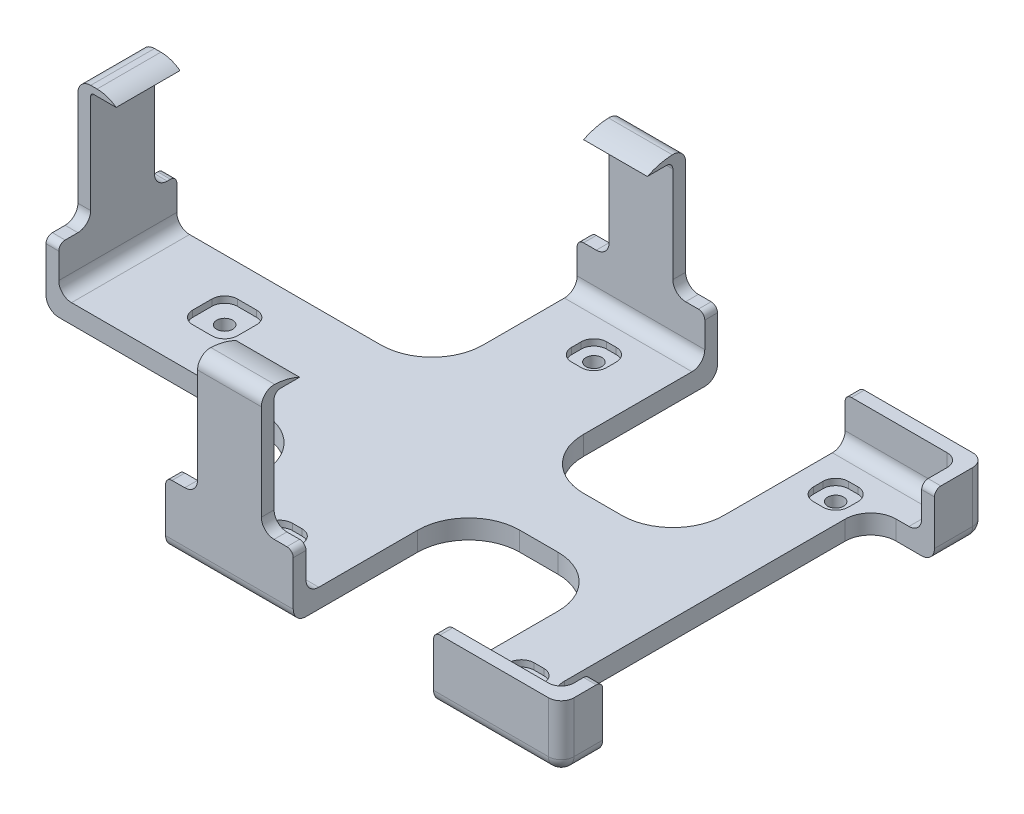
SolidWorks part; units mm, degrees
note: The reader was unsure of these and kept them because the rebuilt part matched: shared geometry of "Sketch1<3>".
ref_plane "Front Plane" through (0, 0, 0) normal (0, 0, 1) x (1, 0, 0)
ref_plane "Top Plane" through (0, 0, 0) normal (0, 1, 0) x (1, 0, 0)
ref_plane "Right Plane" through (0, 0, 0) normal (1, 0, 0) x (0, 0, -1)
sketch "Sketch1" plane through (0, 0, 0) normal (0, 1, 0) x (1, 0, 0)
  line L0 (100, 0) -> (0, 0)
  line L1 (0, 0) -> (0, -62.5)
  line L2 (0, -62.5) -> (100, -62.5)
  line L3 (100, -62.5) -> (100, 0)
  line L4 (102, 2) -> (-2, 2)
  line L5 (-2, 2) -> (-2, -64.5)
  line L6 (-2, -64.5) -> (102, -64.5)
  line L7 (102, -64.5) -> (102, 2)
  dimension "D1" = 62.5
  dimension "D2" = 100
  dimension "D3" = 2
extrude "Boss-Extrude1" add sketch "Sketch1" along normal blind 3 contours L0 L1 L2 L3
extrude "Boss-Extrude2" add sketch "Sketch1<3>" along normal blind 10
sketch "Sketch1<3>" plane through (0, 0, 0) normal (0, 1, 0) x (1, 0, 0) same geometry as "Sketch1"
sketch "Sketch2" plane through (102, 0, 0) normal (1, 0, 0) x (0, 0, -1)
  line L0 (-66, 5) -> (-58, 5) construction
  line L1 (-32, 0) -> (-32, 7.4819) construction
  line L2 (2, 5) -> (-6, 5) construction
  line L3 (-58, 0) -> (-58, 10)
  line L4 (-6, 0) -> (-6, 10)
  line L5 (-64.5, 10) -> (2, 10) construction
  line L6 (-58, 10) -> (-6, 10)
  line L7 (-64.5, 0) -> (2, 0) construction
  line L8 (-58, 0) -> (-6, 0)
  dimension "D1" = 8
extrude "Cut-Extrude1" cut sketch "Sketch2" against normal blind 10
sketch "Sketch5" plane through (0, 0, 64.5) normal (0, 0, 1) x (1, 0, 0)
  line L0 (50, 10) -> (50, 28) construction
  line L1 (-2, 10) -> (102, 10) construction
  line L2 (50, 10) -> (45, 10)
  line L3 (50, 10) -> (55, 10)
  line L4 (45, 10) -> (45, 28)
  line L5 (45, 28) -> (55, 28)
  line L6 (55, 28) -> (55, 10)
  dimension "D1" = 18
  dimension "D2" = 5
  dimension "D3" = 5
extrude "Boss-Extrude3" add sketch "Sketch5" against normal blind 2
sketch "Sketch7" plane through (55, 0, 0) normal (1, 0, 0) x (0, 0, -1)
  line L0 (-62.5, 28) -> (-58.5, 28)
  line L1 (-58.5, 28) -> (-58.5, 29)
  line L2 (-64.5, 28) -> (-64.5, 29)
  line L3 (-64.5, 29) -> (-58.5, 29)
  line L4 (-62.5, 28) -> (-64.5, 28) construction
  line L5 (-62.5, 28) -> (-64.5, 28)
  dimension "D1" = 1
  dimension "D2" = 4
extrude "Boss-Extrude4" add sketch "Sketch7" against normal up to surface (10 mm away) up to face at (45, 19, 63.5)
fillet "Fillet2" radius 10 1 edges at (50, 29, 58.5)
fillet "Fillet4" radius 1 1 edges at (50, 28, 62.5)
fillet "Fillet5" [suppressed] radius 1
sketch "Sketch9" plane through (0, 3, 0) normal (0, 1, 0) x (1, 0, 0)
  line L0 (-2, -32) -> (92, -32) construction
  line L1 (-2, 2) -> (-2, -64.5) construction
  line L2 (92, -58) -> (92, -6) construction
ref_plane "Plane1" through (0, 0, 32) normal (0, 0, 1) x (1, 0, 0)
mirror "Mirror5" about plane through (0, 0, 32) normal (0, 0, 1) of "Boss-Extrude4", "Boss-Extrude3"
fillet "Fillet9" radius 10 1 edges at (50, 29, 5.5)
fillet "Fillet10" radius 0.5 1 edges at (50, 28, 1.5)
fillet "Fillet11" radius 1 1 edges at (50, 29, -0.5)
sketch "Sketch10" plane through (-2, 0, 0) normal (-1, 0, 0) x (0, 0, 1)
  line L0 (31.25, 10) -> (31.25, 28) construction
  line L1 (-2, 10) -> (64.5, 10) construction
  line L2 (36.25, 10) -> (26.25, 10)
  line L3 (26.25, 10) -> (26.25, 28)
  line L4 (26.25, 28) -> (36.25, 28)
  line L5 (36.25, 10) -> (36.25, 28)
  dimension "D1" = 18
  dimension "D2" = 5
extrude "Boss-Extrude5" add sketch "Sketch10" against normal up to surface (2 mm away) up to face at (0, 6.5, 31.25)
sketch "Sketch11" plane through (0, 0, 26.25) normal (0, 0, -1) x (-1, 0, 0)
  line L0 (2, 28) -> (2, 29)
  line L1 (0, 28) -> (-4, 28)
  line L2 (0, 28) -> (2, 28) construction
  line L3 (0, 28) -> (2, 28)
  line L4 (-4, 28) -> (-4, 29)
  line L5 (-4, 29) -> (2, 29)
  dimension "D1" = 1
  dimension "D2" = 4
extrude "Boss-Extrude6" add sketch "Sketch11" against normal up to surface (10 mm away) up to face at (-1, 19, 36.25)
fillet "Fillet12" radius 5 1 edges at (4, 29, 31.25)
fillet "Fillet13" radius 0.5 1 edges at (0, 28, 31.25)
fillet "Fillet14" radius 2 1 edges at (-2, 29, 31.25)
sketch "Sketch14" plane through (0, 3, 0) normal (0, 1, 0) x (1, 0, 0)
  line L0 (0, -62.5) -> (100, -62.5) construction
  line L1 (0, -62.5) -> (100, -62.5) construction
  line L2 (50, -62.5) -> (50, -51.3755) construction
  line L3 (50, -62.5) -> (40, -62.5) construction
  line L4 (0, 0) -> (0, -62.5) construction
  line L5 (0, 0) -> (0, -62.5) construction
  line L6 (0, -31.25) -> (0, -41.25) construction
  line L7 (40, -62.5) -> (40, -41.25)
  line L8 (40, -41.25) -> (0, -41.25)
  line L9 (0, -41.25) -> (-2, -41.25)
  line L10 (-2, -36.25) -> (-2, -64.5) construction
  line L11 (-2, -41.25) -> (-2, -64.5)
  line L12 (-2, -64.5) -> (40, -64.5)
  line L13 (-2, -64.5) -> (45, -64.5) construction
  line L14 (40, -64.5) -> (40, -62.5)
  dimension "D1" = 10
  dimension "D2" = 10
extrude "Cut-Extrude2" cut sketch "Sketch14" against normal through all both and the other way through all
fillet "Fillet15" radius 8 1 edges at (40, 1.5, 41.25)
mirror "Mirror6" about plane through (0, 0, 32) normal (0, 0, 1) of "Cut-Extrude2"
fillet "Fillet16" radius 8 1 edges at (40, 1.5, 22.75)
sketch "Sketch17" plane through (0, 3, 0) normal (0, 1, 0) x (1, 0, 0)
  line L0 (55, -5.5) -> (55, -1.1411) construction
  line L1 (55, -5.5) -> (55, -1.1411) construction
  line L3 (100, 0) -> (40, 0) construction
  line L4 (100, 0) -> (40, 0) construction
  line L5 (55, 0) -> (60, 0) construction
  line L6 (60, 0) -> (60, -27)
  line L7 (-2, -32) -> (92, -32) construction
  line L8 (60, -27) -> (82, -27)
  line L9 (92, -58) -> (92, -6) construction
  line L10 (82, -27) -> (82, 2)
  line L11 (102, 2) -> (-2, 2) construction
  line L12 (82, 2) -> (60, 2)
  line L13 (60, 2) -> (60, 0)
  dimension "D1" = 5
  dimension "D2" = 5
  dimension "D3" = 10
extrude "Cut-Extrude5" cut sketch "Sketch17" against normal through all both and the other way through all
mirror "Mirror7" about plane through (0, 0, 32) normal (0, 0, 1) of "Cut-Extrude5"
fillet "Fillet17" radius 8 4 edges at (82, 1.5, 37) (82, 1.5, 27) (60, 1.5, 27) (60, 1.5, 37)
fillet "Fillet18" radius 4 2 edges at (92, 1.5, 58) (92, 1.5, 6)
fillet "Fillet19" [suppressed] radius 2
fillet "Fillet20" [suppressed] radius 2
fillet "Fillet21" [suppressed] radius 4
fillet "Fillet22" radius 2 2 edges at (100, 6.5, 62.5) (100, 6.5, 0)
fillet "Fillet23" [suppressed] radius 2
fillet "Fillet24" radius 2 2 edges at (102, 5, 64.5) (102, 5, -2)
sketch "Sketch19" plane through (0, 3, 0) normal (0, 1, 0) x (1, 0, 0)
  line L0 (16, -41.25) -> (16, -48.9913) construction
  line L1 (32, -41.25) -> (0, -41.25) construction
  line L2 (12, -41.25) -> (12, -45.25)
  line L3 (12, -45.25) -> (16, -45.25)
  line L4 (16, -45.25) -> (16, -41.25)
  line L5 (12, -41.25) -> (16, -41.25)
  dimension "D1" = 4
  dimension "D2" = 4
sketch "Sketch21" plane through (0, 3, 0) normal (0, 1, 0) x (1, 0, 0)
  line L0 (16, -41.25) -> (16, -34.9562) construction
  line L1 (32, -41.25) -> (0, -41.25) construction
  line L2 (18, -33.25) -> (14, -33.25) construction
  line L3 (14, -33.25) -> (14, -29.25) construction
  line L4 (18, -33.25) -> (18, -29.25) construction
  line L5 (14, -29.25) -> (18, -29.25) construction
  line L7 (19.5, -34.75) -> (19.5, -27.75)
  line L8 (12.5, -27.75) -> (19.5, -27.75)
  line L9 (12.5, -34.75) -> (12.5, -27.75)
  line L10 (19.5, -34.75) -> (12.5, -34.75)
  point P8 (16, -33.25)
  dimension "D1" = 8
  dimension "D2" = 2
  dimension "D3" = 4
  dimension "D4" = 1.5
extrude "Cut-Extrude6" cut sketch "Sketch21" against normal blind 1
sketch "Sketch24" plane through (0, 2, 0) normal (0, 1, 0) x (1, 0, 0)
  line L0 (12.5, -31.25) -> (19.5, -31.25) construction
  line L1 (12.5, -27.75) -> (12.5, -34.75) construction
  line L2 (19.5, -34.75) -> (19.5, -27.75) construction
  line L3 (16, -27.75) -> (16, -34.75) construction
  line L4 (19.5, -27.75) -> (12.5, -27.75) construction
  line L5 (12.5, -34.75) -> (19.5, -34.75) construction
  circle A0 centre (16, -31.25) radius 1.25
  dimension "D1" = 2.5
extrude "Cut-Extrude8" cut sketch "Sketch24" against normal through all
fillet "Fillet25" radius 2 4 edges at (19.5, 2.5, 34.75) (12.5, 2.5, 34.75) (19.5, 2.5, 27.75) (12.5, 2.5, 27.75)
sketch "Sketch25" plane through (0, 3, 0) normal (0, 1, 0) x (1, 0, 0)
  line L0 (40, -7.375) -> (60, -7.375) construction
  line L1 (40, 0) -> (40, -14.75) construction
  line L2 (60, 0) -> (60, -19) construction
  line L4 (47.25, -4.625) -> (52.75, -4.625)
  line L5 (47.25, -4.625) -> (47.25, -10.125)
  line L6 (47.25, -10.125) -> (52.75, -10.125)
  line L7 (52.75, -4.625) -> (52.75, -10.125)
  line L8 (47.25, -4.625) -> (52.75, -10.125) construction
  line L9 (47.25, -10.125) -> (52.75, -4.625) construction
  point P6 (50, -7.375)
  dimension "D1" = 5.5
  dimension "D2" = 5.5
extrude "Cut-Extrude9" cut sketch "Sketch25" against normal blind 1
sketch "Sketch26" plane through (0, 2, 0) normal (0, 1, 0) x (1, 0, 0)
  line L0 (47.25, -7.375) -> (52.75, -7.375) construction
  line L1 (47.25, -4.625) -> (47.25, -10.125) construction
  line L2 (52.75, -10.125) -> (52.75, -4.625) construction
  line L3 (50, -4.625) -> (50, -10.125) construction
  line L4 (52.75, -4.625) -> (47.25, -4.625) construction
  line L5 (47.25, -10.125) -> (52.75, -10.125) construction
  circle A0 centre (50, -7.375) radius 1.25
  dimension "D1" = 2.5
extrude "Cut-Extrude10" cut sketch "Sketch26" against normal through all
sketch "Sketch27" plane through (0, 3, 0) normal (0, 1, 0) x (1, 0, 0)
  line L0 (82, -6.6736) -> (93.7785, -6.6736) construction
  line L1 (82, -19) -> (82, 0) construction
  line L2 (87.8892, -6.6736) -> (87.8892, -24.5424) construction
  line L3 (50, -7.375) -> (87.8892, -7.375) construction
  line L4 (68.9446, -7.375) -> (68.9446, -22.5612) construction
  arc A0 (96, -6) -> (92, -10) centre (96, -10) ccw construction
ref_plane "Plane2" through (68.9446, 0, 0) normal (-1, 0, 0) x (0, 0, 1)
mirror "Mirror8" about plane through (68.9446, 0, 0) normal (-1, 0, 0) of "Cut-Extrude9", "Cut-Extrude10"
mirror "Mirror9" about plane through (0, 0, 32) normal (0, 0, 1) of "Mirror8", "Cut-Extrude9", "Cut-Extrude10"
fillet "Fillet26" radius 2 4 edges at (47.25, 2.5, 53.875) (52.75, 2.5, 53.875) (52.75, 2.5, 59.375) (47.25, 2.5, 59.375)
fillet "Fillet27" radius 2 4 edges at (47.25, 2.5, 10.125) (47.25, 2.5, 4.625) (52.75, 2.5, 10.125) (52.75, 2.5, 4.625)
fillet "Fillet28" radius 2 4 edges at (90.6392, 2.5, 10.125) (85.1392, 2.5, 10.125) (85.1392, 2.5, 4.625) (90.6392, 2.5, 4.625)
fillet "Fillet29" radius 2 4 edges at (90.6392, 2.5, 59.375) (90.6392, 2.5, 53.875) (85.1392, 2.5, 53.875) (85.1392, 2.5, 59.375)
sketch "Sketch29" plane through (0, 0, -0.5) normal (0, 0, 1) x (1, 0, 0)
  line L4 (-2, 10) -> (-2, 0)
  line L5 (-2, 0) -> (40, 0)
  line L6 (40, 0) -> (40, 10)
  line L7 (40, 10) -> (-2, 10)
  line L8 (-2, 10) -> (-2, 0)
  line L10 (40, 0) -> (40, 10)
  line L11 (40, 10) -> (-2, 10)
  line L12 (-2, 0) -> (40, 0)
  dimension "D1" = 0
extrude "Cut-Extrude12" cut sketch "Sketch29" against normal blind 10
sketch "Sketch31" plane through (0, 0, 0) normal (0, 0, 1) x (1, 0, 0)
  line L4 (60, 3) -> (60, 10)
  line L9 (60, 3) -> (60, 10)
  line L10 (40, 10) -> (40, 3)
  line L11 (40, 3) -> (60, 3)
  line L16 (40, 10) -> (40, 3)
  line L17 (40, 3) -> (60, 3)
  line L20 (60, 10) -> (55, 10)
  line L24 (60, 10) -> (55, 10)
  line L26 (55, 10) -> (45, 10)
  line L28 (55, 10) -> (45, 10)
  line L29 (45, 10) -> (40, 10)
  line L31 (45, 10) -> (40, 10)
  dimension "D1" = 0
extrude "Boss-Extrude8" [suppressed] add sketch "Sketch31" along normal up to surface (1.5 mm away)
sketch "Sketch32" plane through (45, 0, 0) normal (-1, 0, 0) x (0, 0, 1)
  line L6 (1.1411, 29) -> (0.5, 29)
  line L7 (-0.5, 28) -> (-0.5, 10)
  line L8 (-0.5, 10) -> (0, 10)
  line L9 (0, 10) -> (1.5, 10)
  line L10 (1.5, 10) -> (1.5, 27.5)
  line L11 (2, 28) -> (5.5, 28)
  line L12 (1.1411, 29) -> (0.5, 29)
  line L13 (-0.5, 28) -> (-0.5, 10)
  line L14 (-0.5, 10) -> (0, 10)
  line L15 (0, 10) -> (1.5, 10)
  line L16 (1.5, 10) -> (1.5, 27.5)
  line L17 (2, 28) -> (5.5, 28)
  arc A3 (0.5, 29) -> (-0.5, 28) centre (0.5, 28) ccw
  arc A4 (2, 28) -> (1.5, 27.5) centre (2, 27.5) ccw
  arc A5 (5.5, 28) -> (1.1411, 29) centre (1.1411, 19) ccw
  arc A6 (0.5, 29) -> (-0.5, 28) centre (0.5, 28) ccw
  arc A7 (2, 28) -> (1.5, 27.5) centre (2, 27.5) ccw
  arc A8 (5.5, 28) -> (1.1411, 29) centre (1.1411, 19) ccw
  dimension "D1" = 0
extrude "Cut-Extrude13" cut sketch "Sketch32" against normal through all
sketch "Sketch33" plane through (0, 3, 0) normal (0, 1, 0) x (1, 0, 0)
  line L0 (92, -32) -> (24.9791, -32) construction
ref_plane "Plane3" through (0, 0, 32) normal (0, 0, 1) x (1, 0, 0)
sketch "Sketch34" plane through (0, 3, 0) normal (0, 1, 0) x (1, 0, 0)
  line L0 (50, -64.5) -> (50, 2) construction
  line L1 (88.1729, 2) -> (88.1729, -64.5) construction
  line L2 (88.1729, -31.25) -> (-2, -31.0405) construction
ref_plane "Plane4" through (-0.0721, 0, 31.045) normal (0.0023, 0, -1) x (-1, 0, -0.0023)
sketch "Sketch35" plane through (0, 0, -2) normal (0, 0, -1) x (-1, 0, 0)
  line L0 (-45, 27) -> (-45, 10) construction
  line L1 (-45, 27) -> (-45, 10) construction
  line L2 (-55, 10) -> (-55, 27) construction
  line L3 (-55, 10) -> (-55, 27) construction
  line L4 (-55, 10) -> (-55, 28)
  line L5 (-45, 10) -> (-45, 28)
  line L6 (-55, 28) -> (-44.7221, 28)
  line L7 (-60, 10) -> (-40, 10) construction
  line L8 (-55, 10) -> (-45, 10)
  line M7 (-40, 10) -> (-60, 10)
  dimension "D1" = 18
  dimension "D2" = 18
extrude "Boss-Extrude9" add sketch "Sketch35" against normal blind 2 contours L6 L4 L5 M7
sketch "Sketch36" plane through (45, 0, 0) normal (-1, 0, 0) x (0, 0, 1)
  line L0 (-2, 28) -> (-2, 29)
  line L1 (0, 28) -> (4, 28)
  line L2 (0, 28) -> (-2, 28) construction
  line L3 (0, 28) -> (-2, 28)
  line L4 (-2, 29) -> (4, 29)
  line L5 (4, 29) -> (4, 28)
  dimension "D1" = 1
  dimension "D2" = 4
extrude "Boss-Extrude10" add sketch "Sketch36" against normal up to surface (10 mm away) up to face at (55, 19, -1)
fillet "Fillet30" radius 10 1 edges at (50, 29, 4)
fillet "Fillet31" radius 2 9 edges at (100, 3, 59.25) (99.4142, 3, 61.9142) (100, 3, 4) (99.4142, 3, 0.5858) (90, 3, 62.5) (90, 3, 0) (50, 3, 62.5) (50, 3, 0) (0, 3, 32)
fillet "Fillet32" radius 2 2 edges at (50, 29, -2) (50, 29, 64.5)
fillet "Fillet33" radius 2 9 edges at (50, 0, 64.5) (-2, 0, 32) (50, 0, -2) (91, 0, 64.5) (102, 0, 60.25) (91, 0, -2) (101.4142, 0, -1.4142) (101.4142, 0, 63.9142) (102, 0, 3)
fillet "Fillet34" radius 1 8 edges at (60, 10, -1) (82, 10, -1) (101, 10, 6) (101, 10, 58) (82, 10, 63.5) (40, 10, 63.5) (-1, 10, 41.25) (-1, 10, 22.75)
fillet "Fillet35" radius 2 6 edges at (-1, 10, 26.25) (-1, 10, 36.25) (55, 10, 63.5) (45, 10, 63.5) (45, 10, -1) (55, 10, -1)
fillet "Fillet36" radius 1 1 edges at (50, 28, 0)
equation "\"1`\"=2"
